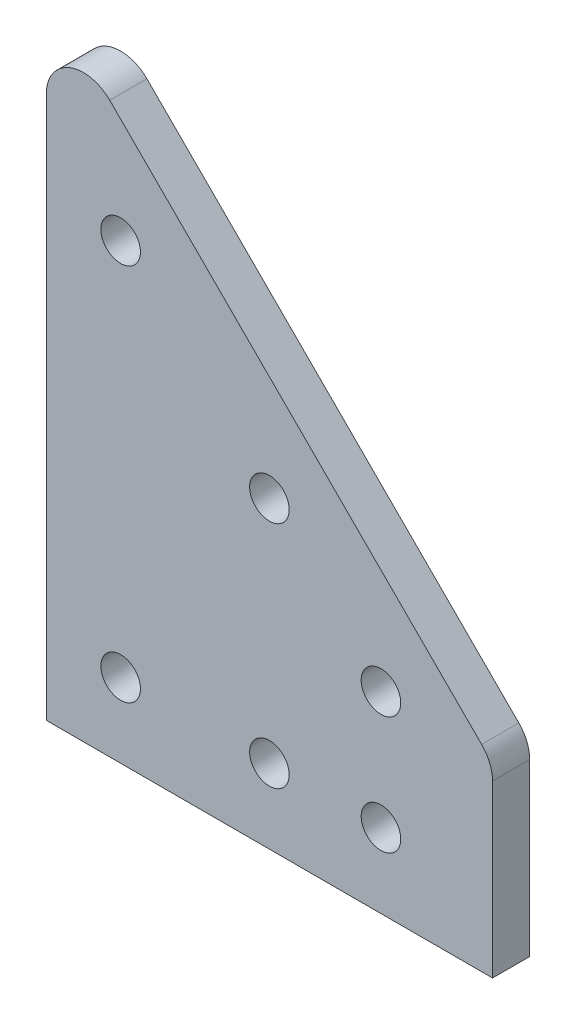
SolidWorks part; units mm, degrees
ref_plane "Front Plane" through (0, 0, 0) normal (0, 0, 1) x (1, 0, 0)
ref_plane "Top Plane" through (0, 0, 0) normal (0, 1, 0) x (1, 0, 0)
ref_plane "Right Plane" through (0, 0, 0) normal (1, 0, 0) x (0, 0, -1)
sketch "Sketch1" plane through (0, 0, 0) normal (0, 0, 1) x (1, 0, 0)
  line L0 (-38.1, -15.875) -> (38.1, -15.875)
  line L1 (38.1, -15.875) -> (38.1, 15.875)
  line L2 (38.1, 15.875) -> (-38.1, 92.075)
  line L3 (-38.1, 92.075) -> (-38.1, -15.875)
  point P3 (0, -15.875)
  point P5 (38.1, 0)
  dimension "D1" = 135
  dimension "D2" = 31.75
  dimension "D3" = 76.2
extrude "Boss-Extrude1" add sketch "Sketch1" along normal mid plane 6.35
hole_wizard "1/4 Clearance Hole1" positions "Sketch2" profile "Sketch3" hole size "1/4" standard "ANSI Inch" end condition through all
sketch "Sketch2" plane through (0, 0, 3.175) normal (0, 0, 1) x (1, 0, 0)
  line L0 (-38.1, 74.1145) -> (38.1, -2.0855)
  line L1 (-38.1, 92.075) -> (-38.1, -15.875) construction
  line L2 (38.1, -15.875) -> (38.1, 15.875) construction
  line L3 (-38.1, -3.175) -> (38.1, -3.175)
  line L5 (38.1, 15.875) -> (-38.1, 92.075) construction
  line L6 (-38.1, -15.875) -> (38.1, -15.875) construction
  point P0 (-25.4, 61.4145)
  point P2 (0, 36.0145)
  point P4 (19.05, 16.9645)
  point P6 (-25.4, -3.175)
  point P8 (19.05, -3.175)
  point P26 (0, -3.175)
  dimension "D1" = 12.7
  dimension "D2" = 12.7
  dimension "D3" = 12.7
  dimension "D4" = 19.05
sketch "Sketch3" plane through (-25.4, 61.4145, 3.175) normal (1, 0, 0) x (0, -1, 0)
  line L0 (0, 0) -> (0, 6.35)
  line L1 (0, 6.35) -> (3.3782, 6.35)
  line L2 (3.3782, 6.35) -> (3.3782, 0)
  line L5 (3.3782, 0) -> (0, 0)
  line L11 (0, -6.35) -> (0, 107.95) construction
  dimension "Thru Hole Dia." = 6.7564
  dimension "Thru Hole Depth" = 6.35
fillet "Fillet1" radius 6.35 2 edges at (38.1, 15.875, 0) (-38.1, 92.075, 0)
